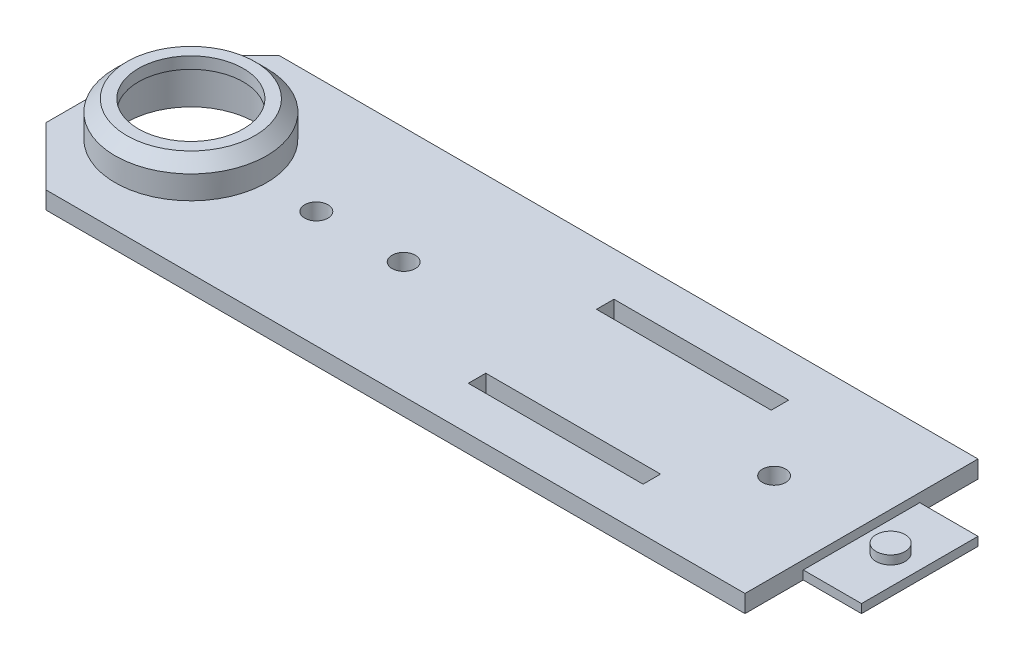
SolidWorks part; units mm, degrees
ref_plane "Alzado" through (0, 0, 0) normal (0, 0, 1) x (1, 0, 0)
ref_plane "Planta" through (0, 0, 0) normal (0, 1, 0) x (1, 0, 0)
ref_plane "Vista lateral" through (0, 0, 0) normal (1, 0, 0) x (0, 0, -1)
sketch "Croquis1" plane through (0, 0, 0) normal (0, 1, 0) x (1, 0, 0)
  line L1 (-65, -20) -> (65, -20)
  line L2 (-65, -20) -> (-65, 20)
  line L3 (-65, 20) -> (65, 20)
  line L4 (65, -20) -> (65, -10)
  line L5 (-65, -20) -> (65, 20) construction
  line L6 (-65, 20) -> (65, -20) construction
  line L10 (0, 0) -> (77.1384, 0) construction
  line L12 (10, 9.5) -> (40, 9.5)
  line L13 (10, 9.5) -> (10, 12.5)
  line L14 (10, 12.5) -> (40, 12.5)
  line L15 (40, 9.5) -> (40, 12.5)
  line L16 (10, 9.5) -> (40, 12.5) construction
  line L17 (10, 12.5) -> (40, 9.5) construction
  line L18 (10, -12.5) -> (40, -12.5)
  line L19 (10, -12.5) -> (10, -9.5)
  line L20 (10, -9.5) -> (40, -9.5)
  line L21 (40, -12.5) -> (40, -9.5)
  line L22 (10, -12.5) -> (40, -9.5) construction
  line L23 (10, -9.5) -> (40, -12.5) construction
  line L26 (65, 10) -> (65, 20)
  line L27 (65, 10) -> (75, 10)
  line L28 (75, 10) -> (75, -10)
  line L29 (75, -10) -> (65, -10)
  circle A2 centre (-50.1299, 0) radius 11
  circle A3 centre (-50.1299, 0) radius 12.5 construction
  circle A4 centre (-28.5951, 0) radius 2
  circle A5 centre (-13.5951, 0) radius 2
  circle A6 centre (50, 0) radius 2
  point P0 (0, 0)
  point P19 (25, 11)
  point P35 (25, -11)
  dimension "D8" = 22
  dimension "D12" = 25
  dimension "D13" = 4
  dimension "D14" = 4
  dimension "D17" = 4
  dimension "D1" = 130
  dimension "D2" = 20
  dimension "D3" = 10
  dimension "D6" = 40
  dimension "D9" = 3
  dimension "D10" = 30
  dimension "D11" = 40
  dimension "D15" = 15
  dimension "D16" = 10
  dimension "D18" = 12.5
  dimension "D19" = 12.5
extrude "Saliente-Extruir1" add sketch "Croquis1" along normal blind 3
sketch "Croquis2" plane through (0, 3, 0) normal (0, 1, 0) x (1, 0, 0)
  circle A0 centre (-50.1299, 0) radius 11
  circle A1 centre (-50.1299, 0) radius 13
  dimension "D1" = 2
extrude "Saliente-Extruir2" add sketch "Croquis2" along normal blind 4
sketch "Croquis3" plane through (0, 7, 0) normal (0, 1, 0) x (1, 0, 0)
  circle A0 centre (-50.1299, 0) radius 13
  circle A1 centre (-50.1299, 0) radius 9
  dimension "D1" = 18
extrude "Saliente-Extruir3" add sketch "Croquis3" along normal blind 2
chamfer "Chaflán1" distance 2 angle 45 1 edges at (-50.1299, 9, 13)
chamfer "Chaflán2" distance 10 angle 45 2 edges at (-65, 1.5, 20) (-65, 1.5, -20)
sketch "Croquis6" plane through (0, 3, 0) normal (0, 1, 0) x (1, 0, 0)
  line L0 (65, 0) -> (75, 0) construction
  line L1 (75, -10) -> (65, -10)
  line L2 (75, -10) -> (75, 10)
  line L3 (75, 10) -> (65, 10)
  line L4 (65, -10) -> (65, 10)
  circle A0 centre (70, 0) radius 2.5
  dimension "D1" = 5
extrude "Cortar-Extruir2" cut sketch "Croquis6" against normal blind 1.5
